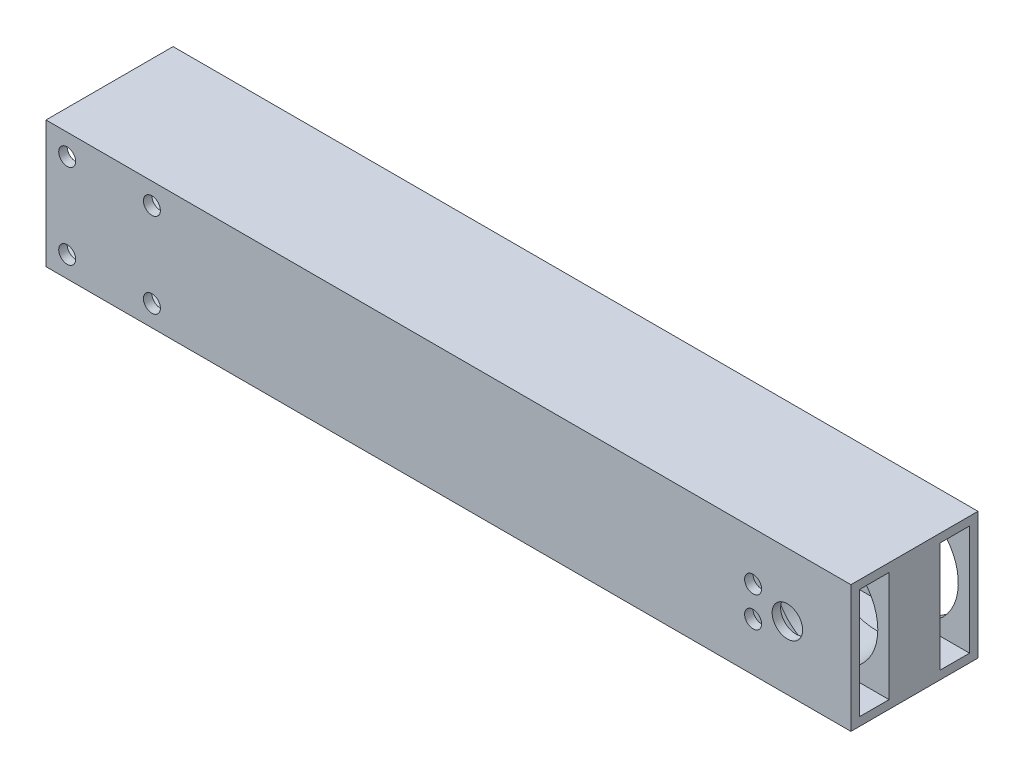
SolidWorks part; units mm, degrees
ref_plane "Front Plane" through (0, 0, 0) normal (0, 0, 1) x (1, 0, 0)
ref_plane "Top Plane" through (0, 0, 0) normal (0, 1, 0) x (1, 0, 0)
ref_plane "Right Plane" through (0, 0, 0) normal (1, 0, 0) x (0, 0, -1)
sketch "Sketch1" plane through (0, 0, 0) normal (1, 0, 0) x (0, 0, -1)
  line L1 (-15, -15) -> (15, -15)
  line L2 (-15, -15) -> (-15, 15)
  line L3 (-15, 15) -> (15, 15)
  line L4 (15, -15) -> (15, 15)
  line L5 (-15, -15) -> (15, 15) construction
  line L6 (-15, 15) -> (15, -15) construction
  line L11 (-5.1844, 5.1844) -> (5.1844, -5.1844) construction
  line L12 (-5.1844, -5.1844) -> (5.1844, 5.1844) construction
  line L13 (-13, 13) -> (-6, 13)
  line L14 (-13, 13) -> (-13, -13)
  line L15 (-13, -13) -> (-6, -13)
  line L16 (-6, 13) -> (-6, -13)
  line L17 (13, 13) -> (6, 13)
  line L18 (13, 13) -> (13, -13)
  line L19 (13, -13) -> (6, -13)
  line L20 (6, 13) -> (6, -13)
  point P0 (0, 0)
  point P7 (0, 0)
  dimension "D1" = 30
  dimension "D2" = 30
  dimension "D3" = 2
  dimension "D4" = 7
  dimension "D5" = 2
  dimension "D6" = 7
  dimension "D7" = 2
  dimension "D8" = 2
extrude "Boss-Extrude3" add sketch "Sketch1" along normal blind 110 and the other way blind 80
sketch "Sketch6" plane through (0, 0, -15) normal (0, 0, -1) x (-1, 0, 0)
  line L0 (-110, -15) -> (-110, 15) construction
  circle A0 centre (-95, 0) radius 12.35
  dimension "D2" = 24.7
  dimension "D1" = 15
extrude "Cut-Extrude5" cut sketch "Sketch6" against normal blind 23
sketch "Sketch8" plane through (0, 0, 15) normal (0, 0, 1) x (1, 0, 0)
  line L0 (110, 15) -> (110, -15) construction
  circle A0 centre (95, 0) radius 3.6
  circle A1 centre (86.9069, 3.5812) radius 2
  circle A2 centre (86.9069, -3.5812) radius 2
  dimension "D2" = 7.2
  dimension "D5" = 4
  dimension "D6" = 4
  dimension "D1" = 15
  dimension "D3" = 8.85
  dimension "D4" = 8.85
extrude "Cut-Extrude6" cut sketch "Sketch8" against normal blind 17
sketch "Sketch9" plane through (-80, 0, 0) normal (-1, 0, 0) x (0, 0, 1)
  line L0 (-6, 13) -> (6, 13)
  line L1 (-6, -13) -> (6, -13)
  line L2 (-6, 13) -> (-6, -13)
  line L3 (6, 13) -> (6, -13)
extrude "Cut-Extrude7" cut sketch "Sketch9" against normal blind 106
sketch "Sketch12" plane through (0, 0, 15) normal (0, 0, 1) x (1, 0, 0)
  line L0 (-80, 15) -> (110, 15) construction
  line L1 (-80, 15) -> (-80, -15) construction
  line L2 (-80, 15) -> (-50, 15) construction
  line L3 (-50, 15) -> (-50, -15) construction
  line L5 (-80, -15) -> (110, -15) construction
  circle A0 centre (-75, 10) radius 2
  circle A2 centre (-55, 10) radius 2
  circle A3 centre (-75, -10) radius 2
  circle A4 centre (-55, -10) radius 2
  point P15 (0, 0)
  point P19 (0, 0)
  point P21 (-50.6474, -19.5931)
  dimension "D3" = 4
  dimension "D7" = 4
  dimension "D9" = 4
  dimension "D11" = 4
  dimension "D1" = 5
  dimension "D2" = 5
  dimension "D4" = 5
  dimension "D5" = 30
  dimension "D6" = 5
  dimension "D8" = 5
  dimension "D10" = 5
  dimension "D12" = 20
  dimension "D13" = 5
extrude "Cut-Extrude8" cut sketch "Sketch12" against normal blind 40 contours A0 | A2 | A3 | A4
